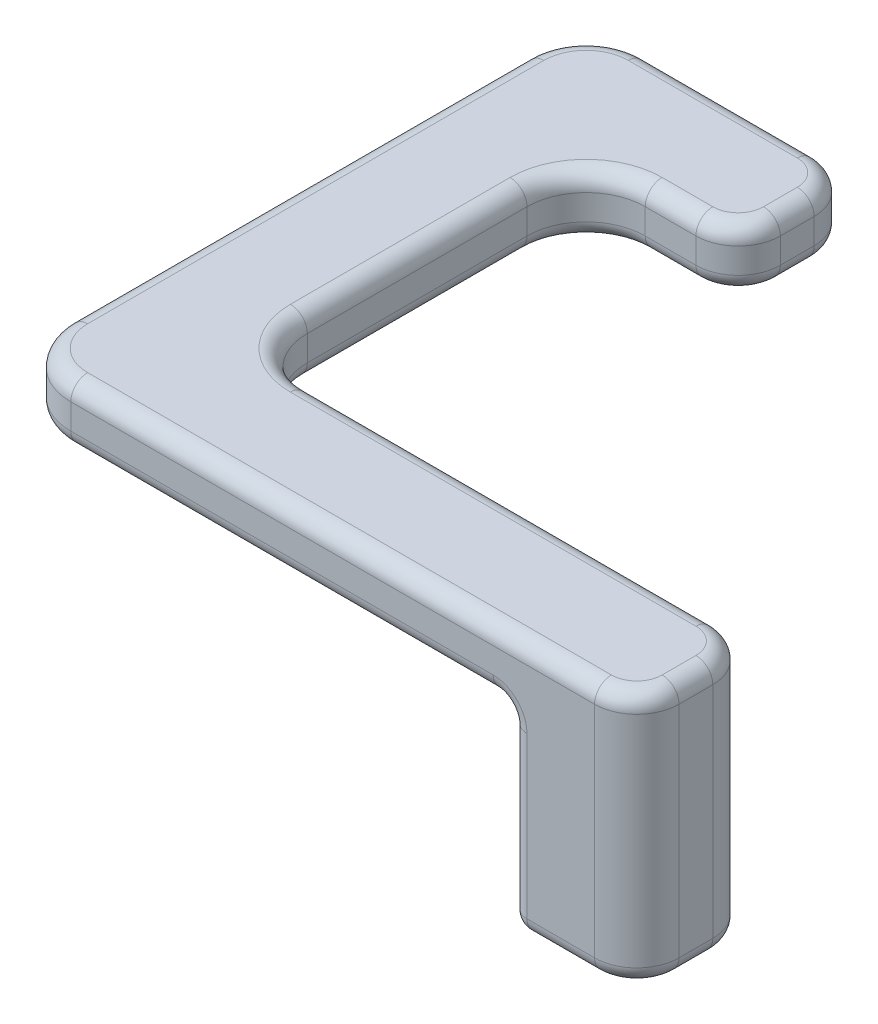
SolidWorks part; units mm, degrees
ref_plane "Front Plane" through (0, 0, 0) normal (0, 0, 1) x (1, 0, 0)
ref_plane "Top Plane" through (0, 0, 0) normal (0, 1, 0) x (1, 0, 0)
ref_plane "Right Plane" through (0, 0, 0) normal (1, 0, 0) x (0, 0, -1)
sketch "Sketch1" plane through (0, 0, 0) normal (0, 1, 0) x (1, 0, 0)
  line L0 (0, 0) -> (0, 20)
  line L1 (0, 20) -> (9, 20)
  line L2 (0, 0) -> (30, 0)
  dimension "D1" = 30
  dimension "D2" = 20
  dimension "D3" = 9
extrude "Extrude-Thin1" add sketch "Sketch1" along normal blind 15 thin thin type one direction wall 7
fillet "Fillet1" radius 2.5 4 edges at (30, 7.5, 7) (30, 7.5, 0) (9, 7.5, -20) (9, 7.5, -27)
fillet "Fillet2" radius 3.5 4 edges at (0, 7.5, 0) (-7, 7.5, 7) (-7, 7.5, -27) (0, 7.5, -20)
sketch "Sketch2" plane through (0, 0, 0) normal (0, -1, 0) x (1, 0, 0)
  line L1 (-22.5, 28) -> (22.5, 28)
  line L2 (-22.5, 28) -> (-22.5, -28)
  line L3 (-22.5, -28) -> (22.5, -28)
  line L4 (22.5, 28) -> (22.5, -28)
  line L5 (-22.5, 28) -> (22.5, -28) construction
  line L6 (-22.5, -28) -> (22.5, 28) construction
  line L7 (6.5, -27) -> (-3.5, -27) construction
  point P0 (0, 0)
  dimension "D1" = 1
  dimension "D2" = 45
extrude "Cut-Extrude1" cut sketch "Sketch2" against normal blind 11.5
fillet "Fillet3" radius 1 38 edges at (22.5, 5.75, 7) (9.5, 11.5, 7) (-5.9749, 11.5, 5.9749) (-7, 11.5, -10) (-5.9749, 11.5, -25.9749) (1.5, 11.5, -27) (8.2678, 11.5, -26.2678) (8.2678, 11.5, -20.7322) (5, 11.5, -20) (1.0251, 11.5, -18.9749) (0, 11.5, -10) (1.0251, 11.5, -1.0251) (13, 11.5, 0) (5, 15, -20) (1.0251, 15, -18.9749) (0, 15, -10) (1.0251, 15, -1.0251) (15.5, 15, 0) (29.2678, 15, 0.7322) (29.2678, 15, 6.2678) (12, 15, 7) (-5.9749, 15, 5.9749) (-7, 15, -10) (-5.9749, 15, -25.9749) (1.5, 15, -27) (8.2678, 15, -26.2678) (25, 0, 7) (29.2678, 0, 6.2678) (29.2678, 0, 0.7322) (25, 0, 0) (22.5, 0, 3.5) (8.2678, 15, -20.7322) (22.5, 5.75, 0) (22.5, 11.5, 3.5) (9, 11.5, -23.5) (30, 15, 3.5) (9, 15, -23.5) (30, 0, 3.5)
sketch "Sketch3" plane through (0, 0, 0) normal (0, -1, 0) x (1, 0, 0)
  line L0 (27.5, 0) -> (23.5, 0) construction
  circle A0 centre (26.0622, 3.5) radius 2.25
  dimension "D1" = 4.5
  dimension "D2" = 3.5
extrude "Cut-Extrude2" cut sketch "Sketch3" against normal blind 2.55
